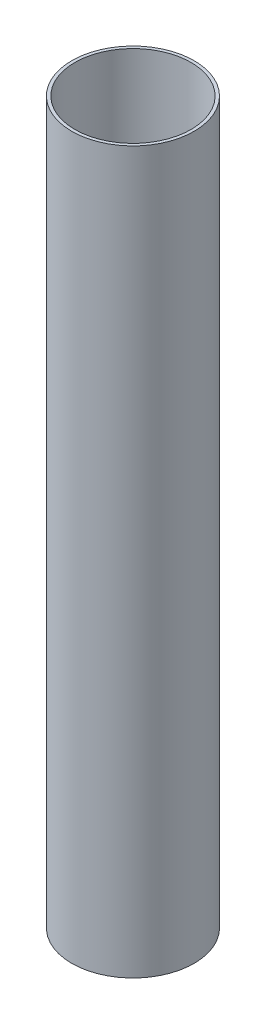
SolidWorks part; units mm, degrees
material "S-Glass Fiber"
ref_plane "Front Plane" through (0, 0, 0) normal (0, 0, 1) x (1, 0, 0)
ref_plane "Top Plane" through (0, 0, 0) normal (0, 1, 0) x (1, 0, 0)
ref_plane "Right Plane" through (0, 0, 0) normal (1, 0, 0) x (0, 0, -1)
sketch "Sketch1" plane through (0, 0, 0) normal (0, 1, 0) x (1, 0, 0)
  circle A0 centre (0, 0) radius 32.258
  circle A1 centre (0, 0) radius 33.9725
  dimension "D1" = 64.516
  dimension "D2" = 67.945
extrude "Boss-Extrude1" add sketch "Sketch1" along normal blind 400
